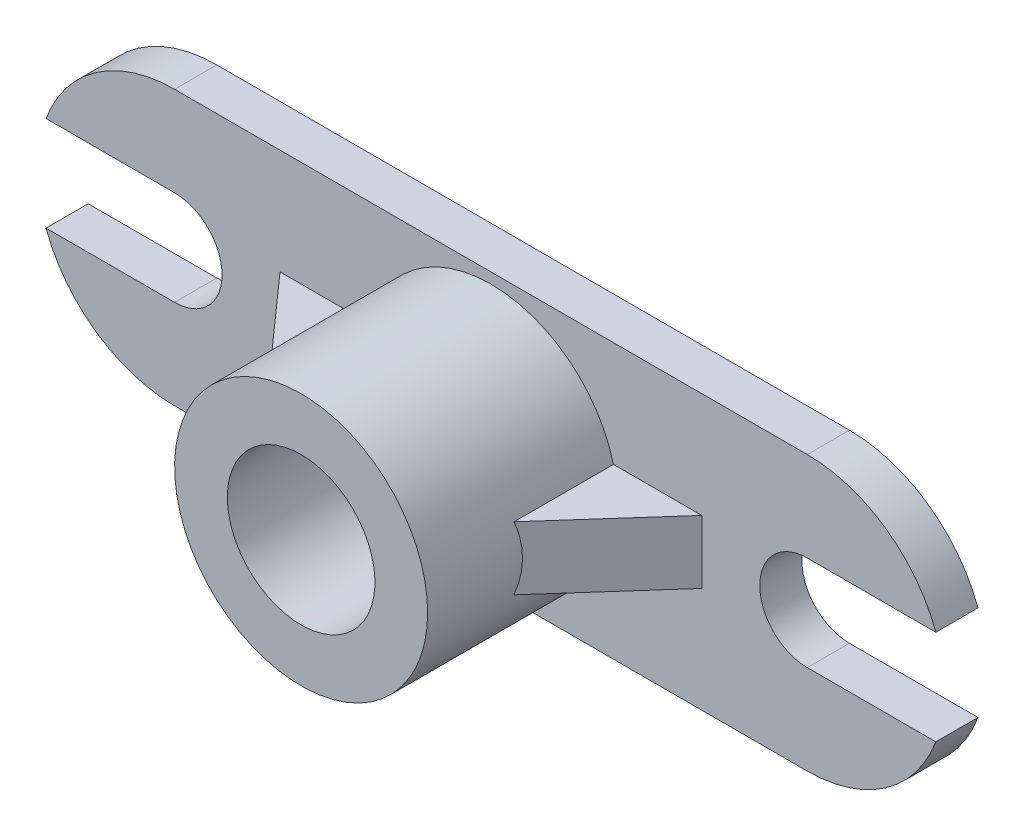
SolidWorks part; units mm, degrees
ref_plane "Спереди" through (0, 0, 0) normal (0, 0, 1) x (1, 0, 0)
ref_plane "Сверху" through (0, 0, 0) normal (0, 1, 0) x (1, 0, 0)
ref_plane "Справа" through (0, 0, 0) normal (1, 0, 0) x (0, 0, -1)
sketch "Эскиз1" plane through (0, 0, 0) normal (0, 0, 1) x (1, 0, 0)
  line L0 (0, 0) -> (30, 0) construction
  line L1 (0, 6.5) -> (30, 6.5)
  line L2 (0, -6.5) -> (30, -6.5)
  line L3 (0, 0) -> (-13, 0) construction
  line L4 (0, -2.25) -> (-13, -2.25)
  line L5 (0, 2.25) -> (-13, 2.25)
  line L6 (30, 0) -> (43, 0) construction
  line L7 (30, 2.25) -> (43, 2.25)
  line L8 (30, -2.25) -> (43, -2.25)
  arc A0 (0, 6.5) -> (0, -6.5) centre (0, 0) ccw
  arc A1 (30, -6.5) -> (30, 6.5) centre (30, 0) ccw
  circle A2 centre (15, 0) radius 6
  circle A3 centre (15, 0) radius 3.5
  arc A4 (0, -2.25) -> (0, 2.25) centre (0, 0) ccw
  arc A5 (-13, 2.25) -> (-13, -2.25) centre (-13, 0) ccw
  arc A6 (30, 2.25) -> (30, -2.25) centre (30, 0) ccw
  arc A7 (43, -2.25) -> (43, 2.25) centre (43, 0) ccw
  point P3 (15, 0)
  point P13 (-6.5, 0)
  point P18 (36.5, 0)
  dimension "D3" = 12
  dimension "D4" = 7
  dimension "D1" = 13
  dimension "D2" = 30
  dimension "D5" = 4.5
extrude "Бобышка-Вытянуть1" add sketch "Эскиз1" along normal blind 2 contours A6 L7 A1 L1 A0 L5 A4 L4 L2 L8 A2 region at (15, 6.0585, 0)
extrude "Бобышка-Вытянуть2" add sketch "Эскиз1<3>" along normal blind 11 contours A2 A3 region at (9.1697, 0, 0)
sketch "Эскиз1<3>" plane through (0, 0, 0) normal (0, 0, 1) x (1, 0, 0) same geometry as "Эскиз1"
sketch "Эскиз2" plane through (0, 0, 0) normal (0, 1, 0) x (1, 0, 0)
  line L0 (5, -2) -> (9, -6.5)
  line L1 (0, -2) -> (30, -2) construction
  line L2 (9, -2) -> (9, -11) construction
  point P6 (15, -2)
  dimension "D1" = 10
rib "Ребро1" sketch "Эскиз2" sketch "Эскиз2" thickness 3 extrusion direction parallel to sketch draft on no parameters "D1"=3
pattern_circular "Круговой массив1" count 2 over 360 about axis through (15, 0, 11) along (0, 0, -1) of "Ребро1"
